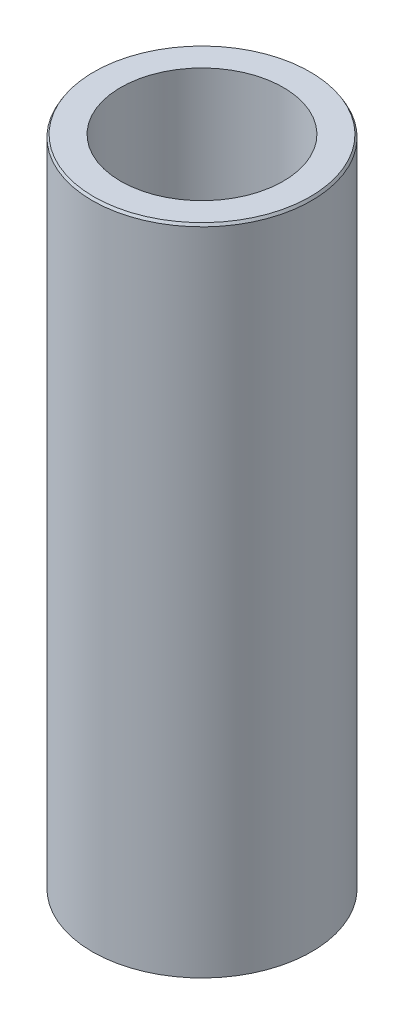
SolidWorks part; units mm, degrees
ref_plane "Front Plane" through (0, 0, 0) normal (0, 0, 1) x (1, 0, 0)
ref_plane "Top Plane" through (0, 0, 0) normal (0, 1, 0) x (1, 0, 0)
ref_plane "Right Plane" through (0, 0, 0) normal (1, 0, 0) x (0, 0, -1)
sketch "Sketch1" plane through (0, 0, 0) normal (0, 1, 0) x (1, 0, 0)
  circle A0 centre (0, 0) radius 40
  dimension "SHAFT_OD" = 80
extrude "Boss-Extrude1" add sketch "Sketch1" along normal blind 238.749
sketch "Sketch2" plane through (0, 0, 0) normal (0, 1, 0) x (1, 0, 0)
  circle A0 centre (0, 0) radius 29.6517
  dimension "BORE_D" = 59.3034
extrude "Cut-Extrude1" cut sketch "Sketch2" along normal through all
chamfer "Chamfer1" distance 0.9471 angle 30 2 edges at (0, 238.749, 40) (0, 0, 40) first distance on face at (0, 238.749, 40) first distance on face at (0, 0, 29.6517)
